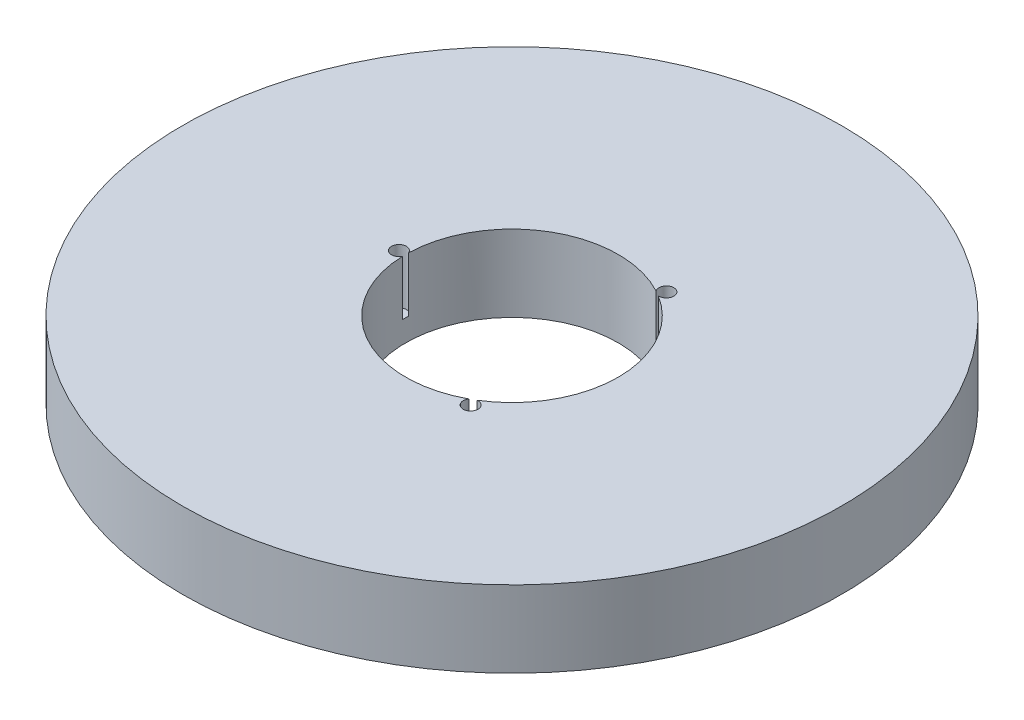
SolidWorks part; units mm, degrees
ref_plane "Front Plane" through (0, 0, 0) normal (0, 0, 1) x (1, 0, 0)
ref_plane "Top Plane" through (0, 0, 0) normal (0, 1, 0) x (1, 0, 0)
ref_plane "Right Plane" through (0, 0, 0) normal (1, 0, 0) x (0, 0, -1)
sketch "Sketch1" plane through (0, 0, 0) normal (0, 1, 0) x (1, 0, 0)
  circle A0 centre (0, 0) radius 77.5
  dimension "FLANGE_OD" = 155
extrude "Boss-Extrude1" add sketch "Sketch1" along normal blind 18
sketch "Sketch2" plane through (0, 0, 0) normal (0, 1, 0) x (1, 0, 0)
  circle A0 centre (0, 0) radius 25
  dimension "BORE_D" = 50
extrude "Cut-Extrude1" cut sketch "Sketch2" along normal through all
sketch "Sketch3" plane through (0, 18, 0) normal (0, 1, 0) x (1, 0, 0)
  circle A0 centre (0, 0) radius 26.5836 construction
  circle A1 centre (-26.5836, 0) radius 1.7435
  dimension "BOLT_D" = 3.487
  dimension "BOLT_PCD" = 53.1673
extrude "Cut-Extrude2" cut sketch "Sketch3" against normal blind 12.8891
pattern_circular "CirPattern1" count 3 over 360 about axis through (0, 0, 0) along (0, 1, 0) of "Cut-Extrude2"
